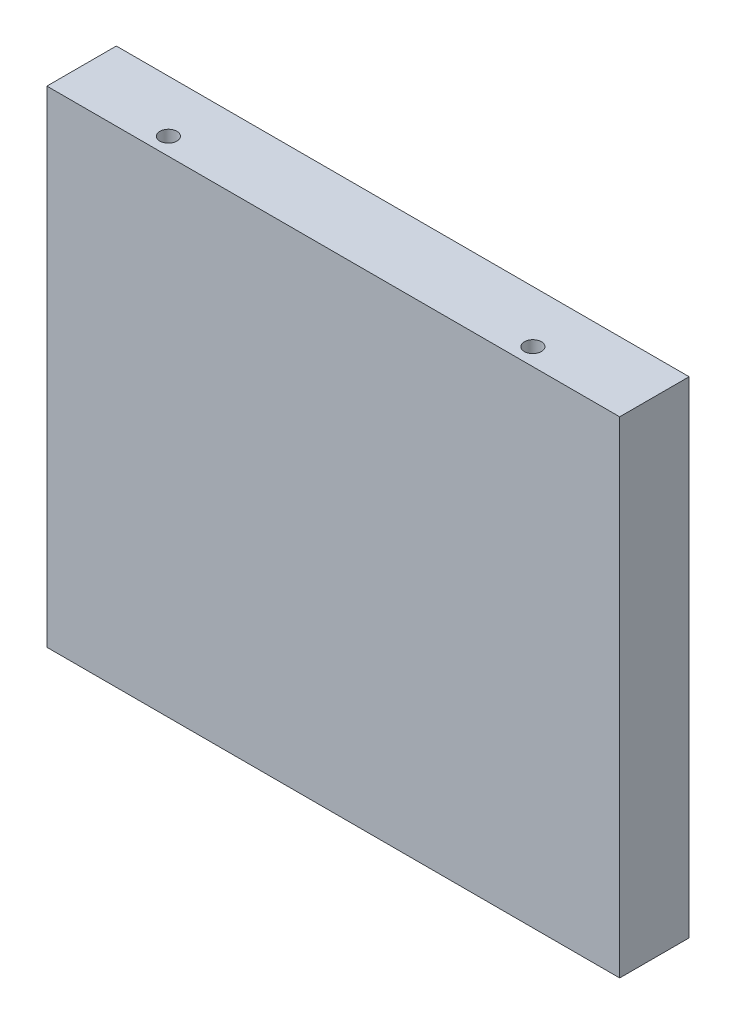
SolidWorks part; units mm, degrees
ref_plane "Front Plane" through (0, 0, 0) normal (0, 0, 1) x (1, 0, 0)
ref_plane "Top Plane" through (0, 0, 0) normal (0, 1, 0) x (1, 0, 0)
ref_plane "Right Plane" through (0, 0, 0) normal (1, 0, 0) x (0, 0, -1)
sketch "Sketch1" plane through (0, 0, 0) normal (0, 0, 1) x (1, 0, 0)
  line L1 (419.1, -355.6) -> (-419.1, -355.6)
  line L2 (419.1, -355.6) -> (419.1, 355.6)
  line L3 (419.1, 355.6) -> (-419.1, 355.6)
  line L4 (-419.1, -355.6) -> (-419.1, 355.6)
  line L5 (419.1, -355.6) -> (-419.1, 355.6) construction
  line L6 (419.1, 355.6) -> (-419.1, -355.6) construction
  point P0 (0, 0)
  dimension "D1" = 838.2
  dimension "D2" = 711.2
extrude "Boss-Extrude1" add sketch "Sketch1" along normal blind 101.6
hole_wizard "Ø25.0mm Dowel Hole1" positions "Sketch2" profile "Sketch3" hole size "Ø25.0" standard "DIN" end condition through all
sketch "Sketch2" plane through (0, -355.6, 0) normal (0, -1, 0) x (-1, 0, 0)
  line L0 (419.1, -76.2) -> (-419.1, -76.2) construction
  line L1 (419.1, -101.6) -> (419.1, 0) construction
  line L2 (-419.1, -101.6) -> (-419.1, 0) construction
  line L4 (419.1, 0) -> (-419.1, 0) construction
  point P0 (266.7, -76.2)
  point P2 (-266.7, -76.2)
  dimension "D1" = 76.2
  dimension "D2" = 152.4
  dimension "D3" = 152.4
sketch "Sketch3" plane through (-266.7, -355.6, 76.2) normal (1, 0, 0) x (0, 0, -1)
  line L0 (0, 0) -> (0, 711.2)
  line L1 (0, 711.2) -> (12.5, 711.2)
  line L2 (12.5, 711.2) -> (12.5, 0)
  line L5 (12.5, 0) -> (0, 0)
  line L11 (0, -6.35) -> (0, 107.95) construction
  dimension "Thru Hole Dia." = 25
  dimension "Thru Hole Depth" = 711.2
